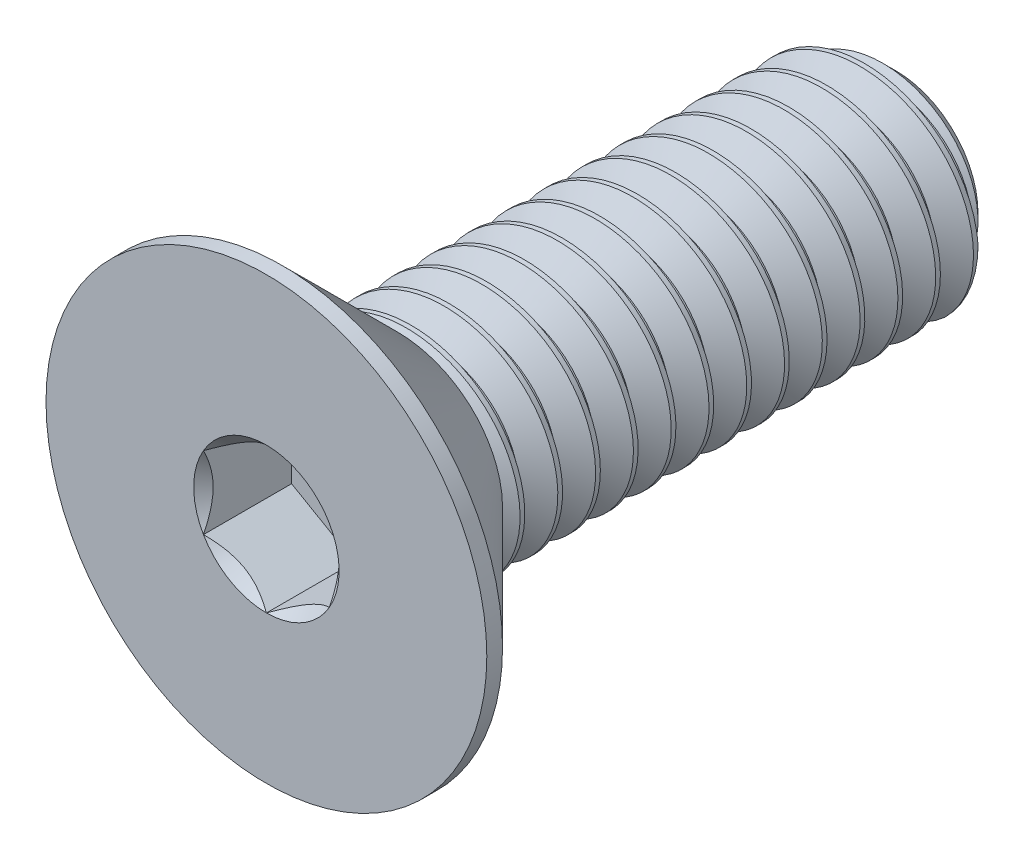
SolidWorks part; units mm, degrees
ref_plane "Front" through (0, 0, 0) normal (0, 0, 1) x (1, 0, 0)
ref_plane "Top" through (0, 0, 0) normal (0, 1, 0) x (1, 0, 0)
ref_plane "Right" through (0, 0, 0) normal (1, 0, 0) x (0, 0, -1)
sketch "Sketch1" plane through (0, 0, 0) normal (1, 0, 0) x (0, 0, -1)
  line L0 (0, 3.5) -> (0.25, 3.5) construction
  line L1 (0.25, 3.5) -> (2, 1.75) construction
  line L2 (0, 1.75) -> (10, 1.75)
  line L3 (10, 1.75) -> (10, 0)
  line L4 (10, 0) -> (0, 0)
  line L5 (0, 0) -> (0, 3.5) construction
  line L6 (0, 3.5) -> (0, -3.5) construction
  line L7 (10, 1.75) -> (10, -1.75) construction
  line L8 (0, -3.5) -> (0.25, -3.5) construction
  line L9 (0.25, -3.5) -> (2, -1.75) construction
  line L11 (0, 1.75) -> (0, 0)
  line L12 (2, 1.75) -> (2, 0) construction
revolve "Revolve1" add sketch "Sketch1" angle 360 mid plane about L4
sketch "Sketch3" plane through (0, 0, -10) normal (0, 0, -1) x (-1, 0, 0)
  circle A0 centre (0, 0) radius 1.75
curve "Helix/Spiral1" pitch 0.6 height 10 radius 1.75 centre (0, 0, -10) axis (0, 0, 1) start towards (0, 1, 0)
sketch "Sketch2" plane through (0, 0, 0) normal (1, 0, 0) x (0, 0, -1)
  line L0 (10, 1.75) -> (10.525, 1.75)
  line L1 (10.525, 1.75) -> (10.3, 1.3603)
  line L2 (10.3, 1.3603) -> (10.225, 1.3603)
  line L3 (10.225, 1.3603) -> (10, 1.75)
  line L4 (10.1125, 1.5551) -> (10.4125, 1.5551) construction
  dimension "D1" = 60
  dimension "D2" = 0.075
  dimension "D3" = 0.3
chamfer "Chamfer1" distance 0.45 angle 45 1 edges at (0, 1.75, -10)
sweep "Cut-Sweep1" cut profiles "Sketch2" path "Helix/Spiral1" align with end faces yes
sketch "Sketch7" plane through (0, 0, 0) normal (1, 0, 0) x (0, 0, -1)
  line L0 (0, 3.5) -> (0.25, 3.5) construction
  line L1 (0.25, 3.5) -> (2, 1.75) construction
  line L2 (0, 3.5) -> (0.25, 3.5)
  line L3 (0.25, 3.5) -> (2, 1.75)
  line L4 (2, 1.75) -> (2, 0) construction
  line L5 (2, 1.75) -> (2, 0)
  line L7 (0, 0) -> (0, 3.5) construction
  line L8 (0, 0) -> (0, 3.5)
  line L9 (0, 0) -> (2, 0)
  line L10 (3.85, 0) -> (-3.85, 0) construction
revolve "Revolve2" add sketch "Sketch7" angle 360 mid plane about L9
ref_plane "Plane1" through (0, 0, -2) normal (0, 0, 1) x (1, 0, 0)
sketch "Sketch8" plane through (0, 0, -2) normal (0, 0, 1) x (1, 0, 0)
  circle A0 centre (0, 0) radius 1.75
extrude "Boss-Extrude1" add sketch "Sketch8" against normal through all draft 45
sketch "Sketch5" plane through (0, 0, 0) normal (0, 0, 1) x (1, 0, 0)
  line L1 (1, -0.5774) -> (1, 0.5774)
  line L2 (1, 0.5774) -> (0, 1.1547)
  line L3 (0, 1.1547) -> (-1, 0.5774)
  line L4 (-1, 0.5774) -> (-1, -0.5774)
  line L5 (-1, -0.5774) -> (0, -1.1547)
  line L6 (0, -1.1547) -> (1, -0.5774)
  circle A0 centre (0, 0) radius 1 construction
  dimension "Hex" = 2
extrude "Cut-Extrude2" cut sketch "Sketch5" against normal blind 1.4
sketch "Sketch6" plane through (0, 0, 0) normal (0, 0, 1) x (1, 0, 0)
  circle A0 centre (0, 0) radius 1.1547
extrude "Cut-Extrude3" cut sketch "Sketch6" against normal blind 1.4 draft 45
sketch "Sketch9" [suppressed] plane through (0, 0, -5.5) normal (0, 0, 1) x (1, 0, 0)
  circle A1 centre (0, 0) radius 5
  circle A2 centre (0, 0) radius 5
  point P0 (0, 5)
  dimension "D1" = 0
extrude "Boss-Extrude2" [suppressed] add sketch "Sketch9" against normal offset from surface (18.5 mm away) 26 up to face at (0, 1.3, -10)
fillet "Fillet1" [suppressed] radius 0.35
sketch "Sketch10" plane through (0, 0, 0) normal (1, 0, 0) x (0, 0, -1)
  line L0 (10, 1.75) -> (10, -1.75) construction
  point P0 (9.1, -1.75)
  dimension "D1" = 0.9
equation "\"D3@Helix/Spiral1\" = \"Lg@Sketch1\""
equation "\"D2@Sketch2\" = \"D4@Helix/Spiral1\" * .125"
equation "\"D3@Sketch2\" = \"D4@Helix/Spiral1\" * .5"
equation "\"D1@Chamfer1\" = \"D4@Helix/Spiral1\" * .75"
equation "\"D1@Cut-Extrude2\" = \"Head Ht@Sketch1\" * .7"
equation "\"D1@Sketch10\" = \"D4@Helix/Spiral1\" * 1.5"
equation "\"D1@Cut-Extrude3\" = \"D1@Cut-Extrude2\""
equation "\"D1@Fillet1\" = \"Dia@Sketch1\" * .1"
